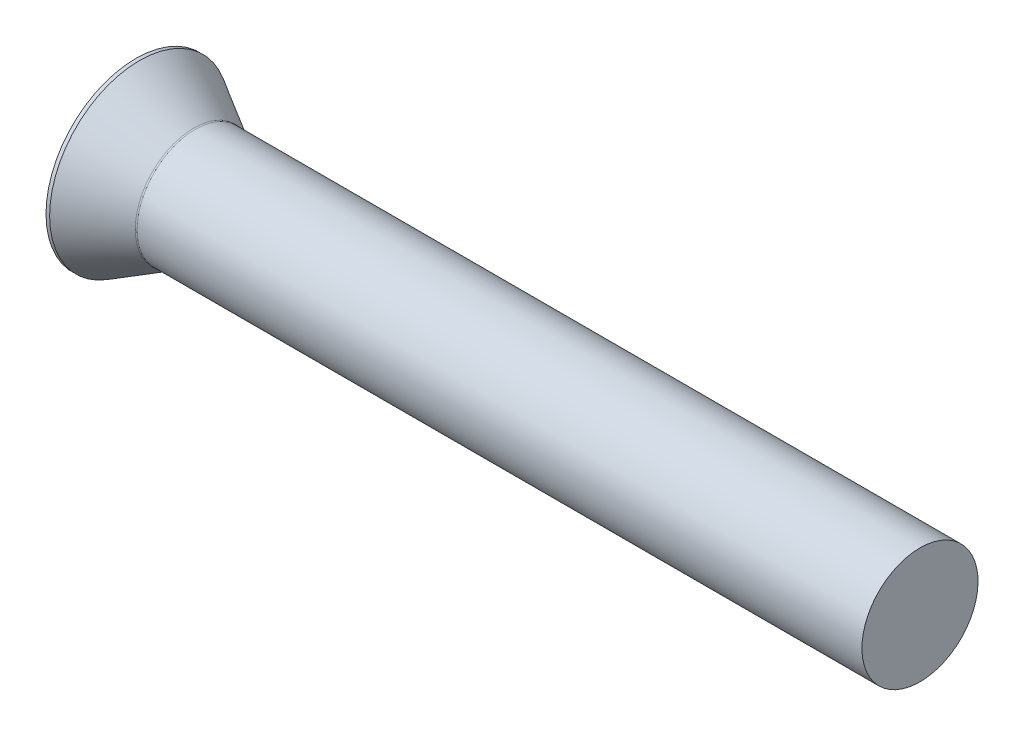
SolidWorks part; units mm, degrees
ref_plane "Front" through (0, 0, 0) normal (0, 0, 1) x (1, 0, 0)
ref_plane "Top" through (0, 0, 0) normal (0, 1, 0) x (1, 0, 0)
ref_plane "Right" through (0, 0, 0) normal (1, 0, 0) x (0, 0, -1)
sketch "Sketch3" plane through (19.4681, 10.942, 0) normal (0, 0, 1) x (0, 1, 0)
  line L0 (-10.942, 30.4893) -> (-10.942, -15.4792) construction
  line L3 (-2.942, 8.0681) -> (-10.942, 8.0681)
  line L4 (-2.942, 8.0681) -> (1.4324, 15.6448)
  line L5 (1.4324, 15.6448) -> (1.4324, 16.1448)
  line L6 (-10.942, 19.4681) -> (-10.942, 8.0681)
  arc A0 (1.4324, 16.1448) -> (-10.942, 19.4681) centre (-10.942, -5.2319) ccw
  dimension "D1" = 8
revolve "BaseHead" add sketch "Sketch3" angle 360 about L0
sketch "Sketch2" plane through (11.4, 0.1081, -0.5592) normal (1, 0, 0) x (0, 0, -1)
  circle A0 centre (-0.5592, -0.1081) radius 8
  circle A1 centre (-0.5592, -0.1081) radius 8 construction
extrude "BaseBody" add sketch "Sketch2" along normal blind 100
fillet "Fillet1" radius 0.4 1 edges at (11.4, 8, 0)
equation "\"D1@Sketch3\"=\"d@Sketch2\"/2"
